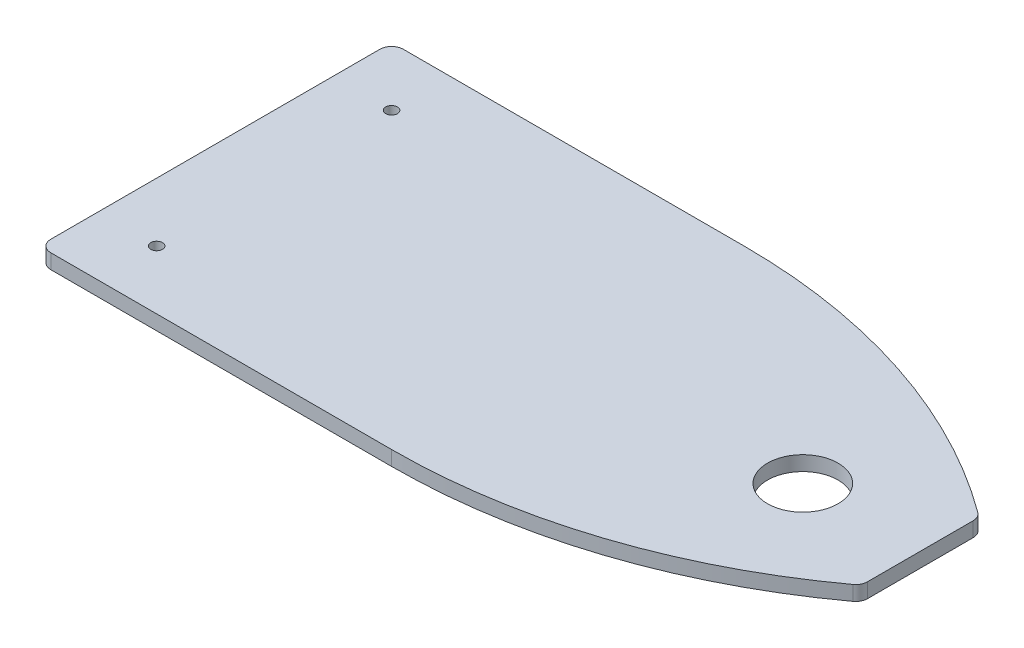
SolidWorks part; units mm, degrees
ref_plane "Front" through (0, 0, 0) normal (0, 0, 1) x (1, 0, 0)
ref_plane "Top" through (0, 0, 0) normal (0, 1, 0) x (1, 0, 0)
ref_plane "Right" through (0, 0, 0) normal (1, 0, 0) x (0, 0, -1)
sketch "Sketch1" plane through (0, 0, 0) normal (0, 1, 0) x (1, 0, 0)
  line L1 (76.2, -38.1) -> (-76.2, -38.1)
  line L2 (76.2, -38.1) -> (76.2, 38.1)
  line L3 (76.2, 38.1) -> (-76.2, 38.1)
  line L4 (-76.2, -38.1) -> (-76.2, 38.1)
  line L5 (76.2, -38.1) -> (-76.2, 38.1) construction
  line L6 (76.2, 38.1) -> (-76.2, -38.1) construction
  point P0 (0, 0)
  dimension "D1" = 76.2
  dimension "D2" = 152.4
extrude "Boss-Extrude1" add sketch "Sketch1" along normal blind 3.175
sketch "Sketch4" plane through (0, 3.175, 0) normal (0, 1, 0) x (1, 0, 0)
  line L0 (0, 38.1) -> (76.2, 38.1)
  line L1 (76.2, 38.1) -> (-76.2, 38.1) construction
  line L2 (76.2, 38.1) -> (76.2, 12.7)
  line L3 (76.2, -38.1) -> (76.2, 38.1) construction
  line L4 (76.2, -38.1) -> (76.2, -12.7)
  line L5 (76.2, -38.1) -> (0, -38.1)
  line L6 (-76.2, -38.1) -> (76.2, -38.1) construction
  arc A0 (0, -38.1) -> (76.2, -12.7) centre (0, 88.9) ccw
  arc A1 (0, 38.1) -> (76.2, 12.7) centre (0, -88.9) cw
  dimension "D3" = 127
  dimension "D4" = 127
  dimension "D1" = 25.4
  dimension "D2" = 25.4
extrude "Cut-Extrude1" cut sketch "Sketch4" against normal blind 3.175
fillet "Fillet2" radius 2.54 2 edges at (76.2, 1.5875, 12.7) (76.2, 1.5875, -12.7)
fillet "Fillet3" radius 2.54 2 edges at (-76.2, 1.5875, 38.1) (-76.2, 1.5875, -38.1)
sketch "Sketch5" plane through (0, 3.175, 0) normal (0, 1, 0) x (1, 0, 0)
  line L0 (-55, 0) -> (55, 0) construction
  line L1 (76.2, -11.422) -> (76.2, 11.422) construction
  circle A0 centre (50.8, 0) radius 7.62
  dimension "D1" = 15.24
  dimension "D2" = 25.4
extrude "Cut-Extrude2" cut sketch "Sketch5" against normal blind 3.175
sketch "Sketch6" plane through (0, 3.175, 0) normal (0, 1, 0) x (1, 0, 0)
  line L0 (0, 38.1) -> (-73.66, 38.1) construction
  line L1 (-73.66, -38.1) -> (0, -38.1) construction
  line L2 (-76.2, 35.56) -> (-76.2, -35.56) construction
  circle A0 centre (-63.5, 25.4) radius 1.27
  circle A1 centre (-63.5, -25.4) radius 1.27
  dimension "D1" = 2.54
  dimension "D2" = 2.54
  dimension "D4" = 12.7
  dimension "D3" = 12.7
  dimension "D5" = 12.7
  dimension "D6" = 12.7
extrude "Cut-Extrude3" cut sketch "Sketch6" against normal blind 3.175
